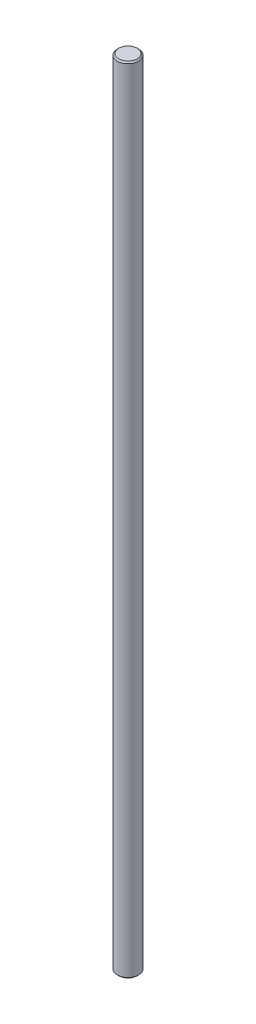
SolidWorks part; units mm, degrees
ref_plane "Front Plane" through (0, 0, 0) normal (0, 0, 1) x (1, 0, 0)
ref_plane "Top Plane" through (0, 0, 0) normal (0, 1, 0) x (1, 0, 0)
ref_plane "Right Plane" through (0, 0, 0) normal (1, 0, 0) x (0, 0, -1)
sketch "Sketch1" plane through (0, 0, 0) normal (0, 1, 0) x (1, 0, 0)
  circle A0 centre (0, 0) radius 4
  dimension "D1" = 8
extrude "Boss-Extrude1" add sketch "Sketch1" along normal blind 150 and the other way blind 150
chamfer "Chamfer1" distance 0.5 angle 45 2 edges at (0, -150, 4) (0, 150, 4)
